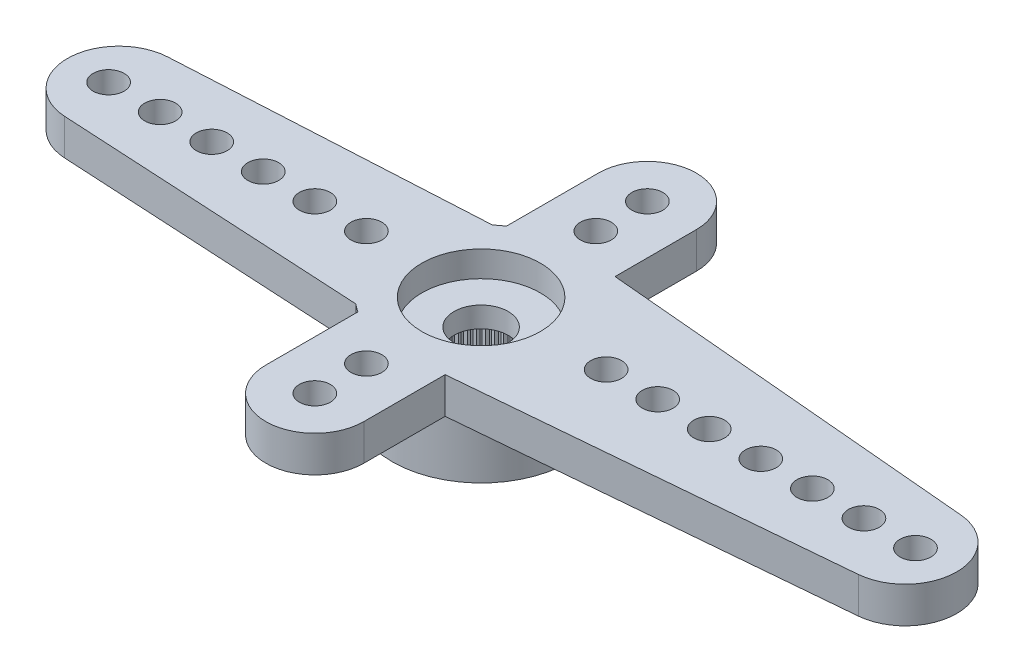
SolidWorks part; units mm, degrees
material "PVC Rígido"
ref_plane "Plano frontal" through (0, 0, 0) normal (0, 0, 1) x (1, 0, 0)
ref_plane "Plano superior" through (0, 0, 0) normal (0, 1, 0) x (1, 0, 0)
ref_plane "Plano direito" through (0, 0, 0) normal (1, 0, 0) x (0, 0, -1)
sketch "Esboço1" plane through (0, 0, 0) normal (0, 1, 0) x (1, 0, 0)
  line L0 (0, 0) -> (-14.05, 0) construction
  line L1 (-14.1591, 1.997) -> (-2.2091, 2.65)
  line L2 (-2.2091, -2.65) -> (-14.1591, -1.997)
  arc A0 (-2.2091, -2.65) -> (-2.2091, 2.65) centre (0, 0) ccw
  arc A1 (-14.1591, 1.997) -> (-14.1591, -1.997) centre (-14.05, 0) ccw
  dimension "D1" = 6.9
  dimension "D2" = 4
  dimension "D3" = 19.5
  dimension "D4" = 5.3
extrude "Ressalto-extrusão1" add sketch "Esboço1" against normal blind 1.4
sketch "Esboço2" plane through (0, -1.4, 0) normal (0, -1, 0) x (1, 0, 0)
  arc A0 (-2.2091, -2.65) -> (-2.2091, 2.65) centre (0, 0) ccw construction
  circle A1 centre (0, 0) radius 3.45
extrude "Ressalto-extrusão2" add sketch "Esboço2" along normal offset from surface (2.4 mm away) 3.8 up to face at (-7.242, 0, 0)
hole_wizard "Furo1" positions "Esboço9" profile "Esboço10" legacy end condition through all
sketch "Esboço9" plane through (0, 0, 0) normal (0, 1, 0) x (1, 0, 0)
  line L1 (-14.45, 0) -> (0, 0) construction
  arc A2 (-14.1591, 1.997) -> (-14.1591, -1.997) centre (-14.05, 0) ccw construction
  point P0 (-14.45, 0)
  point P19 (-16.05, 0)
  dimension "D1" = 1.6
sketch "Esboço10" plane through (-14.45, 0, 0) normal (1, 0, 0) x (0, 0, 1)
  line L0 (0, 0) -> (0, 3.8)
  line L1 (0, 3.8) -> (0.6, 3.8)
  line L2 (0.6, 3.8) -> (0.6, 0)
  line L3 (0.6, 0) -> (0, 0)
  line L4 (0, 110) -> (0, -10) construction
  dimension "Diameter" = 1.2
  dimension "Depth" = 3.8
pattern_linear "Padrão linear1" count 6 spacing 2 along (1, 0, 0) of "Furo1"
sketch "Esboço12" plane through (0, 0, 0) normal (0, 1, 0) x (1, 0, 0)
  line L0 (0.3041, 3.4366) -> (16.6263, 1.9922)
  line L1 (16.6263, -1.9922) -> (0.3041, -3.4366)
  arc A0 (-2.2091, -2.65) -> (-2.2091, 2.65) centre (0, 0) ccw construction
  arc A1 (0.3041, -3.4366) -> (0.3041, 3.4366) centre (0, 0) ccw
  arc A2 (16.6263, 1.9922) -> (16.6263, -1.9922) centre (16.45, 0) cw
  arc A3 (-14.1591, 1.997) -> (-14.1591, -1.997) centre (-14.05, 0) ccw construction
  dimension "D1" = 2
  dimension "D2" = 34.5
extrude "Ressalto-extrusão3" add sketch "Esboço12" against normal up to surface (1.4 mm away) up to face at (-12.45, -1.4, 0.6)
hole_wizard "Furo2" positions "Esboço13" profile "Esboço14" legacy end condition through all
sketch "Esboço13" plane through (0, 0, 0) normal (0, 1, 0) x (1, 0, 0)
  line L0 (0, 0) -> (16.85, 0) construction
  arc A0 (16.6263, -1.9922) -> (16.6263, 1.9922) centre (16.45, 0) ccw construction
  point P0 (16.85, 0)
  point P6 (18.45, 0)
  dimension "D1" = 1.6
sketch "Esboço14" plane through (16.85, 0, 0) normal (1, 0, 0) x (0, 0, 1)
  line L0 (0, 0) -> (0, 3.8)
  line L1 (0, 3.8) -> (0.6, 3.8)
  line L2 (0.6, 3.8) -> (0.6, 0)
  line L3 (0.6, 0) -> (0, 0)
  line L4 (0, 110) -> (0, -10) construction
  dimension "Diameter" = 1.2
  dimension "Depth" = 3.8
pattern_linear "Padrão linear2" count 7 spacing 2 along (-1, 0, 0) of "Furo2"
sketch "Esboço16" plane through (0, 0, 0) normal (0, 1, 0) x (1, 0, 0)
  line L0 (0, -6.45) -> (0, 6.45) construction
  line L1 (-1.9, -6.45) -> (-1.9, 6.45)
  line L2 (1.9, -6.45) -> (1.9, 6.45)
  arc A0 (-1.9, -6.45) -> (1.9, -6.45) centre (0, -6.45) ccw
  arc A1 (1.9, 6.45) -> (-1.9, 6.45) centre (0, 6.45) ccw
  point P2 (0, 0)
  dimension "D2" = 16.7
  dimension "D1" = 3.8
extrude "Ressalto-extrusão4" add sketch "Esboço16" against normal up to surface (1.4 mm away) up to face at (14.85, -1.4, 0.6)
hole_wizard "Furo3" positions "Esboço17" profile "Esboço18" legacy end condition through all
sketch "Esboço17" plane through (0, 0, 0) normal (0, 1, 0) x (1, 0, 0)
  point P0 (0, -6.45)
sketch "Esboço18" plane through (0, 0, 6.45) normal (1, 0, 0) x (0, 0, 1)
  line L0 (0, 0) -> (0, 3.8)
  line L1 (0, 3.8) -> (0.6, 3.8)
  line L2 (0.6, 3.8) -> (0.6, 0)
  line L3 (0.6, 0) -> (0, 0)
  line L4 (0, 110) -> (0, -10) construction
  dimension "Diameter" = 1.2
  dimension "Depth" = 3.8
pattern_linear "Padrão linear3" count 2 spacing 2 along (0, 0, -1) of "Furo3"
pattern_circular "PadrãoCircular1" count 2 over 360 about axis through (0, -1.4, 0) along (0, 1, 0) of "Padrão linear3"
hole_wizard "Furo4" positions "Esboço3" profile "Esboço4" legacy
sketch "Esboço3" plane through (0, -3.8, 0) normal (0, -1, 0) x (-1, 0, 0)
  point P0 (0, 0)
sketch "Esboço4" plane through (0, -3.8, 0) normal (1, 0, 0) x (0, 0, -1)
  line L0 (0, 0) -> (0, 2)
  line L1 (0, 2) -> (2.475, 2)
  line L2 (2.475, 2) -> (2.475, 0)
  line L3 (2.475, 0) -> (0, 0)
  line L4 (0, 110) -> (0, -10) construction
  dimension "Diameter" = 4.95
  dimension "Depth" = 2
hole_wizard "Furo5" positions "Esboço5" profile "Esboço6" legacy
sketch "Esboço5" plane through (0, 0, 0) normal (0, 1, 0) x (1, 0, 0)
  point P0 (0, 0)
sketch "Esboço6" plane through (0, 0, 0) normal (1, 0, 0) x (0, 0, 1)
  line L0 (0, 0) -> (0, 1)
  line L1 (0, 1) -> (2.3, 1)
  line L2 (2.3, 1) -> (2.3, 0)
  line L3 (2.3, 0) -> (0, 0)
  line L4 (0, 110) -> (0, -10) construction
  dimension "Diameter" = 4.6
  dimension "Depth" = 1
hole_wizard "Furo6" positions "Esboço7" profile "Esboço8" legacy end condition through all
sketch "Esboço7" plane through (0, 0, 0) normal (0, 1, 0) x (1, 0, 0)
  point P0 (0, 0)
sketch "Esboço8" plane through (0, 0, 0) normal (1, 0, 0) x (0, 0, 1)
  line L0 (0, 0) -> (0, 3.8)
  line L1 (0, 3.8) -> (1.05, 3.8)
  line L2 (1.05, 3.8) -> (1.05, 0)
  line L3 (1.05, 0) -> (0, 0)
  line L4 (0, 110) -> (0, -10) construction
  dimension "Diameter" = 2.1
  dimension "Depth" = 3.8
sketch "Esboço11" plane through (0, -3.8, 0) normal (0, -1, 0) x (1, 0, 0)
  line L0 (-0.0981, 2.4731) -> (0, 2.375)
  line L1 (0, 2.375) -> (0.0981, 2.4731)
  line L2 (0, 0) -> (0, 2.475) construction
  circle A0 centre (0, 0) radius 2.375 construction
  circle A1 centre (0, 0) radius 2.475
  arc A2 (0.0981, 2.4731) -> (-0.0981, 2.4731) centre (0, 0) ccw
  dimension "D3" = 4.75
  dimension "D2" = 0.1
  dimension "D1" = 0
extrude "Ressalto-extrusão5" add sketch "Esboço11" against normal up to surface (2 mm away) up to face at (0, -1.8, 1.05)
pattern_circular "PadrãoCircular2" count 60 over 360 about axis through (0, -1.4, 0) along (0, 1, 0) of "Ressalto-extrusão5"
sketch "Sketch1" plane through (0, 0, 0) normal (0, 1, 0) x (1, 0, 0)
  line L0 (-8.45, 0) -> (8.85, 0) construction
  circle A0 centre (0, 0) radius 1.05
  circle A1 centre (0, 0) radius 2.3
  circle A2 centre (4.85, 0) radius 0.6
  circle A3 centre (6.85, 0) radius 0.6
  circle A4 centre (8.85, 0) radius 0.6
  circle A5 centre (-4.45, 0) radius 0.6
  circle A6 centre (-6.45, 0) radius 0.6
  circle A7 centre (-8.45, 0) radius 0.6
sketch "Sketch2" plane through (-1.9, 0, 0) normal (-1, 0, 0) x (0, 0, 1)
  line L0 (2.8797, 0) -> (2.8797, -3.8015)
